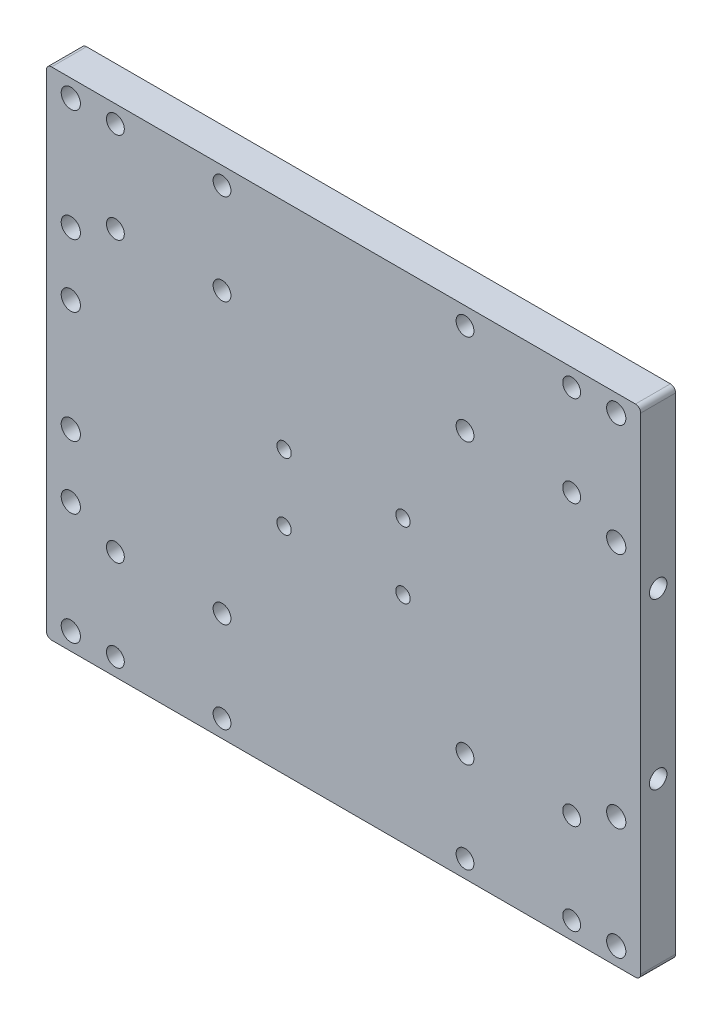
SolidWorks part; units mm, degrees
ref_plane "Front Plane" through (0, 0, 0) normal (0, 0, 1) x (1, 0, 0)
ref_plane "Top Plane" through (0, 0, 0) normal (0, 1, 0) x (1, 0, 0)
ref_plane "Right Plane" through (0, 0, 0) normal (1, 0, 0) x (0, 0, -1)
sketch "Sketch1" plane through (0, 0, 0) normal (0, 0, 1) x (1, 0, 0)
  line L1 (85, -71) -> (-85, -71)
  line L2 (85, -71) -> (85, 71)
  line L3 (85, 71) -> (-85, 71)
  line L4 (-85, -71) -> (-85, 71)
  line L5 (85, -71) -> (-85, 71) construction
  line L6 (85, 71) -> (-85, -71) construction
  point P0 (0, 0)
  dimension "D1" = 170
  dimension "D2" = 142
extrude "Boss-Extrude1" add sketch "Sketch1" along normal mid plane 10
sketch "Sketch2" plane through (0, 0, 5) normal (0, 0, 1) x (1, 0, 0)
  line L0 (-65.25, 71) -> (-65.25, -71) construction
  line L1 (65.25, -71) -> (65.25, 71) construction
  line L2 (-34.75, 71) -> (-34.75, -71) construction
  line L3 (34.75, -71) -> (34.75, 71) construction
  line L4 (70.6711, 66) -> (-71.3289, 66) construction
  line L5 (-71.3289, -66) -> (70.6711, -66) construction
  line L6 (70.6711, 40) -> (-71.3289, 40) construction
  line L7 (-71.3289, -40) -> (70.6711, -40) construction
  line L8 (85, 71) -> (-85, 71) construction
  line L9 (-85, -71) -> (85, -71) construction
  line L10 (-85, 71) -> (-85, -71) construction
  line L11 (85, -71) -> (85, 71) construction
  circle A0 centre (-65.25, 66) radius 2.55
  circle A1 centre (-34.75, 66) radius 2.55
  circle A2 centre (-34.75, 40) radius 2.55
  circle A3 centre (-65.25, 40) radius 2.55
  circle A4 centre (65.25, 66) radius 2.55
  circle A5 centre (65.25, 40) radius 2.55
  circle A6 centre (34.75, 40) radius 2.55
  circle A7 centre (34.75, 66) radius 2.55
  circle A8 centre (-65.25, -40) radius 2.55
  circle A9 centre (-34.75, -40) radius 2.55
  circle A10 centre (-34.75, -66) radius 2.55
  circle A11 centre (-65.25, -66) radius 2.55
  circle A12 centre (34.75, -40) radius 2.55
  circle A13 centre (65.25, -40) radius 2.55
  circle A14 centre (65.25, -66) radius 2.55
  circle A15 centre (34.75, -66) radius 2.55
  dimension "D1" = 5.1
  dimension "D2" = 5.1
  dimension "D3" = 5.1
  dimension "D4" = 5.1
  dimension "D5" = 5.1
  dimension "D6" = 5.1
  dimension "D7" = 5.1
  dimension "D8" = 5.1
  dimension "D9" = 5.1
  dimension "D10" = 5.1
  dimension "D11" = 5.1
  dimension "D12" = 5.1
  dimension "D13" = 5.1
  dimension "D14" = 5.1
  dimension "D15" = 5.1
  dimension "D16" = 5.1
  dimension "D17" = 5
  dimension "D18" = 5
  dimension "D19" = 26
  dimension "D20" = 26
  dimension "D21" = 30.5
  dimension "D22" = 30.5
  dimension "D23" = 19.75
  dimension "D24" = 19.75
extrude "Cut-Extrude1" cut sketch "Sketch2" against normal through all
sketch "Sketch3" plane through (0, 0, 5) normal (0, 0, 1) x (1, 0, 0)
  line L0 (-78, 71) -> (-78, -71) construction
  line L1 (85, 71) -> (-85, 71) construction
  line L2 (-85, -71) -> (85, -71) construction
  line L3 (78, 71) -> (78, -71) construction
  line L4 (-85, 66) -> (85, 66) construction
  line L5 (-85, 71) -> (-85, -71) construction
  line L6 (85, -71) -> (85, 71) construction
  line L7 (-85, 34) -> (85, 34) construction
  line L8 (-85, -34) -> (85, -34) construction
  line L9 (-85, -66) -> (85, -66) construction
  circle A0 centre (-78, 66) radius 2.75
  circle A1 centre (-78, 34) radius 2.75
  circle A2 centre (-78, -34) radius 2.75
  circle A3 centre (-78, -66) radius 2.75
  circle A4 centre (78, 66) radius 2.75
  circle A5 centre (78, 34) radius 2.75
  circle A6 centre (78, -34) radius 2.75
  circle A7 centre (78, -66) radius 2.75
  dimension "D7" = 5.5
  dimension "D8" = 5.5
  dimension "D9" = 5.5
  dimension "D10" = 5.5
  dimension "D11" = 5.5
  dimension "D12" = 5.5
  dimension "D13" = 5.5
  dimension "D14" = 5.5
  dimension "D1" = 5
  dimension "D2" = 32
  dimension "D3" = 5
  dimension "D4" = 32
  dimension "D5" = 7
  dimension "D6" = 7
extrude "Cut-Extrude2" cut sketch "Sketch3" against normal through all
sketch "Sketch4" plane through (0, 0, 5) normal (0, 0, 1) x (1, 0, 0)
  line L1 (-17, -9.5) -> (17, -9.5) construction
  line L2 (-17, -9.5) -> (-17, 9.5) construction
  line L3 (-17, 9.5) -> (17, 9.5) construction
  line L4 (17, -9.5) -> (17, 9.5) construction
  line L5 (-17, -9.5) -> (17, 9.5) construction
  line L6 (-17, 9.5) -> (17, -9.5) construction
  circle A0 centre (-17, 9.5) radius 2.05
  circle A1 centre (-17, -9.5) radius 2.05
  circle A2 centre (17, -9.5) radius 2.05
  circle A3 centre (17, 9.5) radius 2.05
  point P0 (0, 0)
  dimension "D3" = 4.1
  dimension "D4" = 4.1
  dimension "D5" = 4.1
  dimension "D6" = 4.1
  dimension "D1" = 34
  dimension "D2" = 19
extrude "Cut-Extrude3" cut sketch "Sketch4" against normal through all
sketch "Sketch5" plane through (85, 0, 0) normal (1, 0, 0) x (0, 0, -1)
  line L0 (0, 71) -> (0, -71) construction
  line L1 (-5, 71) -> (5, 71) construction
  line L2 (-5, -71) -> (5, -71) construction
  circle A0 centre (0, 23.6) radius 2.5
  circle A1 centre (0, -23.6) radius 2.5
  dimension "D1" = 5
  dimension "D2" = 5
  dimension "D3" = 23.6
  dimension "D4" = 23.6
extrude "Cut-Extrude4" cut sketch "Sketch5" against normal blind 10
sketch "Sketch6" plane through (0, 0, 5) normal (0, 0, 1) x (1, 0, 0)
  line L0 (-78, 34) -> (-78, -34) construction
  line L1 (-78, 0) -> (-85, 0) construction
  line L2 (-85, 71) -> (-85, -71) construction
  circle A0 centre (-78, 16) radius 2.75
  circle A1 centre (-78, -16) radius 2.75
  dimension "D1" = 5.5
  dimension "D2" = 5.5
  dimension "D3" = 16
  dimension "D4" = 16
extrude "Cut-Extrude5" cut sketch "Sketch6" against normal through all
fillet "Fillet1" radius 1.5 4 edges at (-85, -71, 0) (85, -71, 0) (85, 71, 0) (-85, 71, 0)
equation "\"D23@Sketch2\"=5.75+14"
equation "\"D24@Sketch2\"=5.75+14"
equation "\"D6@Sketch4\"=\"D3@Sketch4\""
equation "\"D4@Sketch4\"=\"D3@Sketch4\""
equation "\"D5@Sketch4\"=\"D3@Sketch4\""
equation "\"D3@Sketch5\"=47.2/2"
equation "\"D4@Sketch5\"=47.2/2"
equation "\"D3@Sketch6\"=32/2"
equation "\"D4@Sketch6\"=32/2"
